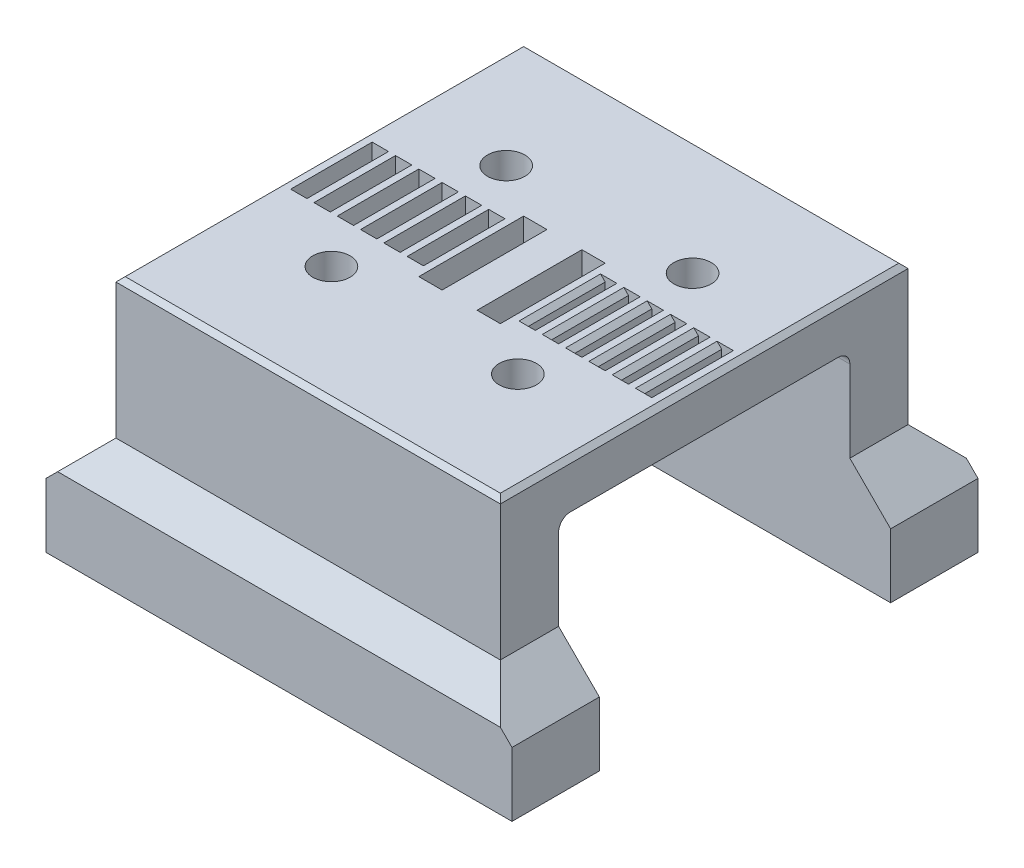
SolidWorks part; units mm, degrees
ref_plane "前视基准面" through (0, 0, 0) normal (0, 0, 1) x (1, 0, 0)
ref_plane "上视基准面" through (0, 0, 0) normal (0, 1, 0) x (1, 0, 0)
ref_plane "右视基准面" through (0, 0, 0) normal (1, 0, 0) x (0, 0, -1)
other "Configuration Table"
sketch "草图1" plane through (0, 0, 0) normal (0, 1, 0) x (1, 0, 0)
  line L1 (0, 0) -> (33, 0)
  line L2 (0, 0) -> (0, -35)
  line L3 (0, -35) -> (33, -35)
  line L4 (33, 0) -> (33, -35)
  circle A0 centre (8.5, -10) radius 1.6
  circle A1 centre (24.5, -10) radius 1.6
  circle A2 centre (24.5, -25) radius 1.6
  circle A3 centre (8.5, -25) radius 1.6
  dimension "D1" = 3.2
  dimension "D4" = 35
  dimension "D5" = 33
  dimension "D6" = 10
  dimension "D7" = 8.5
  dimension "D2" = 2
  dimension "D3" = 2
extrude "凸台-拉伸1" add sketch "草图1" along normal blind 4
sketch "草图2" plane through (0, 4, 0) normal (0, 1, 0) x (1, 0, 0)
  line L0 (0, 0) -> (0, -35) construction
  line L1 (1, -14) -> (2, -14)
  line L2 (1, -14) -> (1, -21)
  line L3 (1, -21) -> (2, -21)
  line L4 (2, -14) -> (2, -21)
  line L5 (3, -14) -> (3, -21)
  line L6 (3, -14) -> (4, -14)
  line L7 (4, -14) -> (4, -21)
  line L8 (3, -21) -> (4, -21)
  line L9 (5, -14) -> (5, -21)
  line L10 (5, -14) -> (6, -14)
  line L11 (6, -14) -> (6, -21)
  line L12 (5, -21) -> (6, -21)
  line L13 (7, -14) -> (7, -21)
  line L14 (7, -14) -> (8, -14)
  line L15 (8, -14) -> (8, -21)
  line L16 (7, -21) -> (8, -21)
  line L17 (9, -14) -> (9, -21)
  line L18 (9, -14) -> (10, -14)
  line L19 (10, -14) -> (10, -21)
  line L20 (9, -21) -> (10, -21)
  line L21 (11, -14) -> (11, -21)
  line L22 (11, -14) -> (12, -14)
  line L23 (12, -14) -> (12, -21)
  line L24 (11, -21) -> (12, -21)
  line L25 (13, -14) -> (13, -21)
  line L26 (13, -14) -> (14, -14)
  line L27 (14, -14) -> (14, -21)
  line L28 (13, -21) -> (14, -21)
  line L29 (15, -14) -> (15, -21)
  line L30 (15, -14) -> (16, -14)
  line L31 (16, -14) -> (16, -21)
  line L32 (15, -21) -> (16, -21)
  line L33 (17, -14) -> (17, -21)
  line L34 (17, -14) -> (18, -14)
  line L35 (18, -14) -> (18, -21)
  line L36 (17, -21) -> (18, -21)
  line L37 (19, -14) -> (19, -21)
  line L38 (19, -14) -> (20, -14)
  line L39 (20, -14) -> (20, -21)
  line L40 (19, -21) -> (20, -21)
  line L41 (21, -14) -> (21, -21)
  line L42 (21, -14) -> (22, -14)
  line L43 (22, -14) -> (22, -21)
  line L44 (21, -21) -> (22, -21)
  line L45 (23, -14) -> (23, -21)
  line L46 (23, -14) -> (24, -14)
  line L47 (24, -14) -> (24, -21)
  line L48 (23, -21) -> (24, -21)
  line L49 (25, -14) -> (25, -21)
  line L50 (25, -14) -> (26, -14)
  line L51 (26, -14) -> (26, -21)
  line L52 (25, -21) -> (26, -21)
  line L53 (27, -14) -> (27, -21)
  line L54 (27, -14) -> (28, -14)
  line L55 (28, -14) -> (28, -21)
  line L56 (27, -21) -> (28, -21)
  line L57 (29, -14) -> (29, -21)
  line L58 (29, -14) -> (30, -14)
  line L59 (30, -14) -> (30, -21)
  line L60 (29, -21) -> (30, -21)
  line L61 (31, -14) -> (31, -21)
  line L62 (31, -14) -> (32, -14)
  line L63 (32, -14) -> (32, -21)
  line L64 (31, -21) -> (32, -21)
  point P6 (1, -17.5)
  point P7 (0, -17.5)
  dimension "D1" = 1
  dimension "D2" = 1
  dimension "D3" = 7
  dimension "D4" = 0
  dimension "D5" = 16
extrude "切除-拉伸1" cut sketch "草图2" against normal blind 1.5
chamfer "倒角1" distance 0.4 angle 45 16 edges at (31, 4, 17.5) (29, 4, 17.5) (27, 4, 17.5) (25, 4, 17.5) (23, 4, 17.5) (21, 4, 17.5) (19, 4, 17.5) (17, 4, 17.5) (14, 4, 17.5) (12, 4, 17.5) (10, 4, 17.5) (6, 4, 17.5) (4, 4, 17.5) (2, 4, 17.5) (16, 4, 17.5) (8, 4, 17.5)
sketch "草图3" plane through (0, 4, 0) normal (0, 1, 0) x (1, 0, 0)
  line L0 (14, -14) -> (13, -14) construction
  line L1 (15, -13) -> (13, -13)
  line L2 (15, -13) -> (15, -22)
  line L3 (15, -22) -> (13, -22)
  line L4 (13, -13) -> (13, -22)
  line L5 (18, -13) -> (20, -13)
  line L6 (18, -13) -> (18, -22)
  line L7 (18, -22) -> (20, -22)
  line L8 (20, -13) -> (20, -22)
  line L9 (13, -21) -> (14, -21) construction
  line L10 (20, -14) -> (18.6, -14) construction
  line L11 (19, -21) -> (20, -21) construction
  dimension "D1" = 1
  dimension "D2" = 1
  dimension "D3" = 1
  dimension "D4" = 1
extrude "切除-拉伸2" cut sketch "草图3" against normal through all
sketch "草图4" plane through (0, 4, 0) normal (0, 1, 0) x (1, 0, 0)
  line L1 (15, -14) -> (18, -14)
  line L2 (15, -14) -> (15, -21)
  line L3 (15, -21) -> (18, -21)
  line L4 (18, -14) -> (18, -21)
extrude "凸台-拉伸2" add sketch "草图4" against normal blind 1.5
sketch "草图5" plane through (0, 0, 0) normal (0, -1, 0) x (-1, 0, 0)
  line L0 (-33, -35) -> (-33, 0) construction
  line L1 (0, -35) -> (-33, -35)
  line L2 (0, -35) -> (0, -30)
  line L3 (0, -30) -> (-33, -30)
  line L4 (-33, -35) -> (-33, -30)
  line L5 (0, 0) -> (0, -35) construction
  line L6 (-33, 0) -> (0, 0)
  line L7 (-33, 0) -> (-33, -5)
  line L8 (-33, -5) -> (0, -5)
  line L9 (0, 0) -> (0, -5)
  dimension "D1" = 5
  dimension "D2" = 5
extrude "凸台-拉伸3" add sketch "草图5" along normal blind 13
sketch "草图7" plane through (0, -13, 0) normal (0, -1, 0) x (-1, 0, 0)
  line L0 (-33, -35) -> (0, -35) construction
  line L1 (3.5, -37.5) -> (-36.5, -37.5)
  line L2 (3.5, -37.5) -> (3.5, -30)
  line L3 (3.5, -30) -> (-36.5, -30)
  line L4 (-36.5, -37.5) -> (-36.5, -30)
  line L5 (0, 0) -> (-33, 0) construction
  line L6 (-36.5, 2.5) -> (3.5, 2.5)
  line L7 (-36.5, 2.5) -> (-36.5, -5)
  line L8 (-36.5, -5) -> (3.5, -5)
  line L9 (3.5, 2.5) -> (3.5, -5)
  line L10 (-33, -5) -> (0, -5) construction
  line L11 (0, -30) -> (-33, -30) construction
  point P4 (-16.5, -37.5)
  point P7 (-16.5, -35)
  point P12 (-16.5, 2.5)
  point P15 (-16.5, 0)
  dimension "D1" = 40
  dimension "D2" = 0
  dimension "D3" = 40
  dimension "D4" = 0
  dimension "D5" = 7.5
  dimension "D6" = 7.5
  dimension "D7" = 0
  dimension "D8" = 0
extrude "凸台-拉伸4" add sketch "草图7" along normal blind 4
chamfer "倒角2" distance 5 angle 45 6 edges at (33, -13, 32.5) (0, -13, 32.5) (16.5, -13, 35) (0, -13, 2.5) (33, -13, 2.5) (16.5, -13, 0)
sketch "草图8" plane through (0, -17, 0) normal (0, -1, 0) x (-1, 0, 0)
  line L0 (-36.5, -37.5) -> (3.5, -37.5) construction
  line L1 (3.5, -37.5) -> (3.5, -30) construction
  circle A0 centre (0.5, -34.5) radius 0.7
  circle A1 centre (-33.5, -34.5) radius 0.7
  circle A2 centre (-33.5, -0.5) radius 0.7
  circle A3 centre (0.5, -0.5) radius 0.7
  dimension "D1" = 1.4
  dimension "D2" = 3
  dimension "D3" = 3
  dimension "D4" = 2
  dimension "D5" = 2
extrude "切除-拉伸3" cut sketch "草图8" against normal blind 7
fillet "圆角1" radius 1 2 edges at (16.5, 0, 30) (16.5, 0, 5)
chamfer "倒角3" distance 0.4 angle 45 4 edges at (33, 4, 17.5) (16.5, 4, 35) (0, 4, 17.5) (16.5, 4, 0)
equation "\"D4@草图1\"=15+20"
equation "\"D5@草图1\"=16+17"
